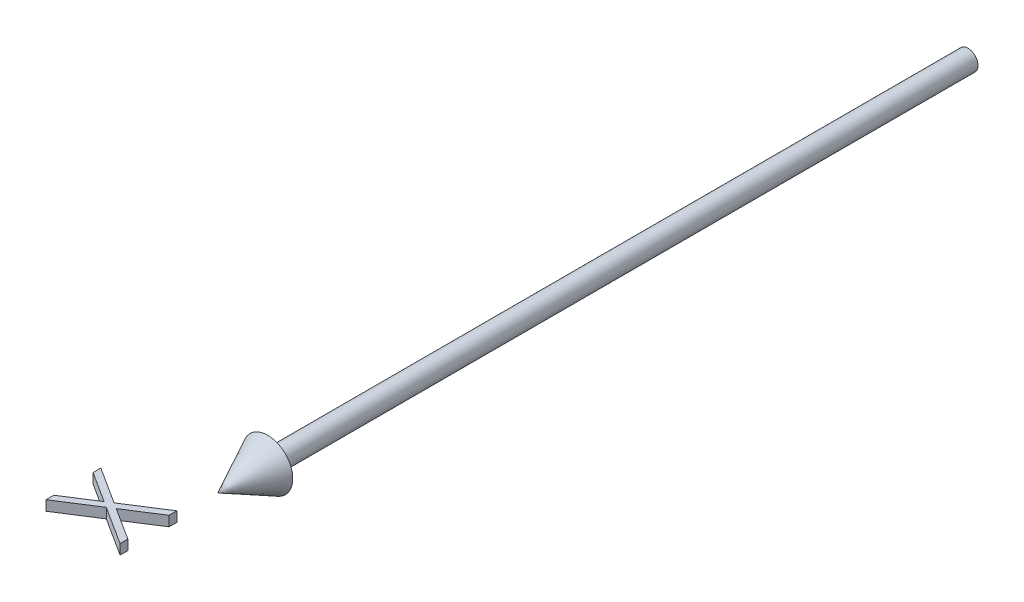
SolidWorks part; units mm, degrees
ref_plane "Front Plane" through (0, 0, 0) normal (0, 0, 1) x (1, 0, 0)
ref_plane "Top Plane" through (0, 0, 0) normal (0, 1, 0) x (1, 0, 0)
ref_plane "Right Plane" through (0, 0, 0) normal (1, 0, 0) x (0, 0, -1)
sketch "Sketch2" plane through (0, 0, 0) normal (0, 1, 0) x (1, 0, 0)
  line L0 (0, 41.95) -> (0, -114.4521) construction
  line L1 (-36.8894, 0) -> (41.4965, 0) construction
  line L2 (0, -150) -> (5, -140)
  line L3 (5, -140) -> (2, -140)
  line L4 (2, -140) -> (2, 0)
  line L5 (2, 0) -> (0, 0)
  line L6 (0, 0) -> (0, -150)
  dimension "D1" = 150
  dimension "D2" = 2
  dimension "D3" = 10
  dimension "D4" = 5
revolve "Revolve1" add sketch "Sketch2" angle 360 about L0
sketch "Sketch3" plane through (0, 0, 0) normal (0, 1, 0) x (1, 0, 0)
  line L0 (0, -157.5) -> (0, -257.0656) construction
  line L1 (-18.6107, 0) -> (18.3141, 0) construction
  line L2 (0, -140) -> (0, 0) construction
  text T0 "X" font "Century Gothic" height 15
  point P3 (0, -231.3063)
  point P9 (0, -152.9602)
  point P10 (0, -257.0656)
  point P11 (0, -169.0339)
  dimension "D1" = 157.5
extrude "Boss-Extrude1" add sketch "Sketch3" against normal blind 1 and the other way blind 1 separate body
equation "\"D1@Sketch2\"=\"frame_arrow_length\""
equation "\"D2@Sketch2\"=\"frame_arrow_odA\"/2"
equation "\"D4@Sketch2\"=\"frame_arrow_head_od\""
equation "\"D3@Sketch2\"=\"frame_arrow_head_length\""
equation "\"frame_arrow_length\"=150"
equation "\"frame_arrow_head_length\"=10"
equation "\"frame_arrow_head_od\"=5"
equation "\"frame_arrow_odA\"=4"
equation "\"D1@Sketch3\"=\"frame_arrow_length\"*1.05"
